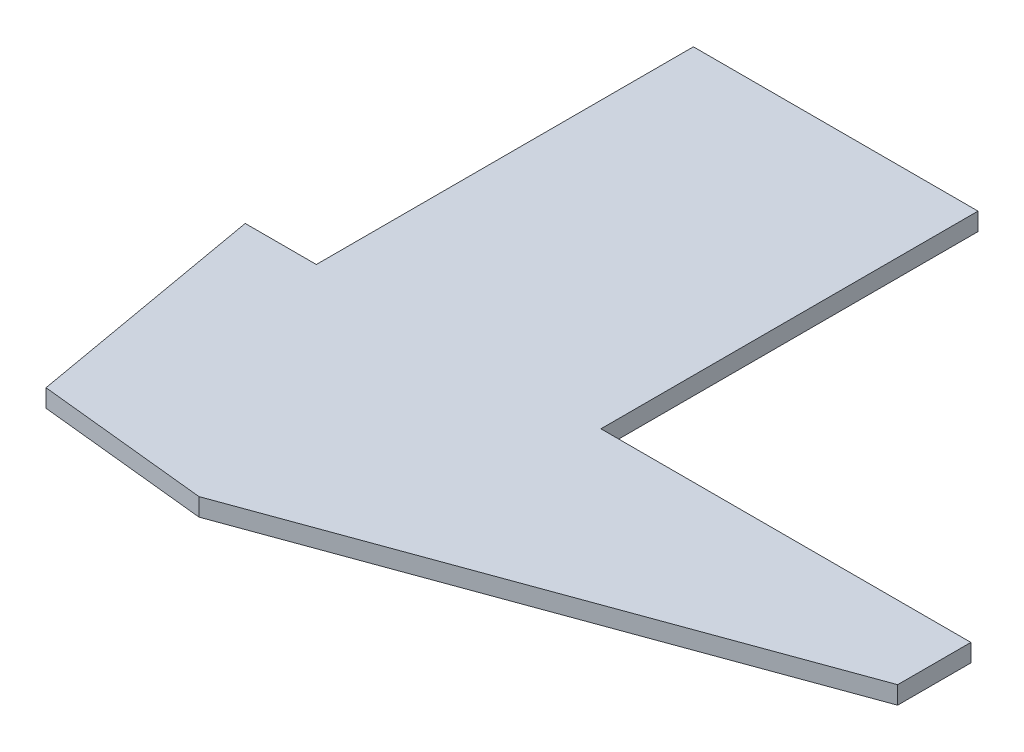
SolidWorks part; units mm, degrees
ref_plane "Front Plane" through (0, 0, 0) normal (0, 0, 1) x (1, 0, 0)
ref_plane "Top Plane" through (0, 0, 0) normal (0, 1, 0) x (1, 0, 0)
ref_plane "Right Plane" through (0, 0, 0) normal (1, 0, 0) x (0, 0, -1)
sketch "Sketch2" plane through (0, 0, 0) normal (0, 1, 0) x (1, 0, 0)
  line L0 (50.8, 0) -> (116.84, 0)
  line L2 (0, 0) -> (0, 67.31)
  line L3 (0, 67.31) -> (50.8, 67.31)
  line L4 (50.8, 0) -> (50.8, 67.31)
  line L5 (-55, 0) -> (55, 0) construction
  line L7 (25.4, -46.355) -> (-5.08, -43.18)
  line L8 (-5.08, -43.18) -> (-12.7, 0)
  line L9 (-12.7, 0) -> (0, 0)
  line L11 (25.4, -46.355) -> (116.84, -13.0736)
  line L12 (116.84, -13.0736) -> (116.84, 0)
  point P5 (-12.7, -43.18)
  point P12 (-2.2476, -41.8958)
  dimension "D1" = 50.8
  dimension "D2" = 67.31
  dimension "D3" = 66.04
  dimension "D4" = 12.7
  dimension "D5" = 43.18
  dimension "D6" = 3.175
  dimension "D7" = 7.62
  dimension "D8" = 110
  dimension "D9" = 30.48
extrude "Boss-Extrude1" add sketch "Sketch2" along normal blind 3.175
